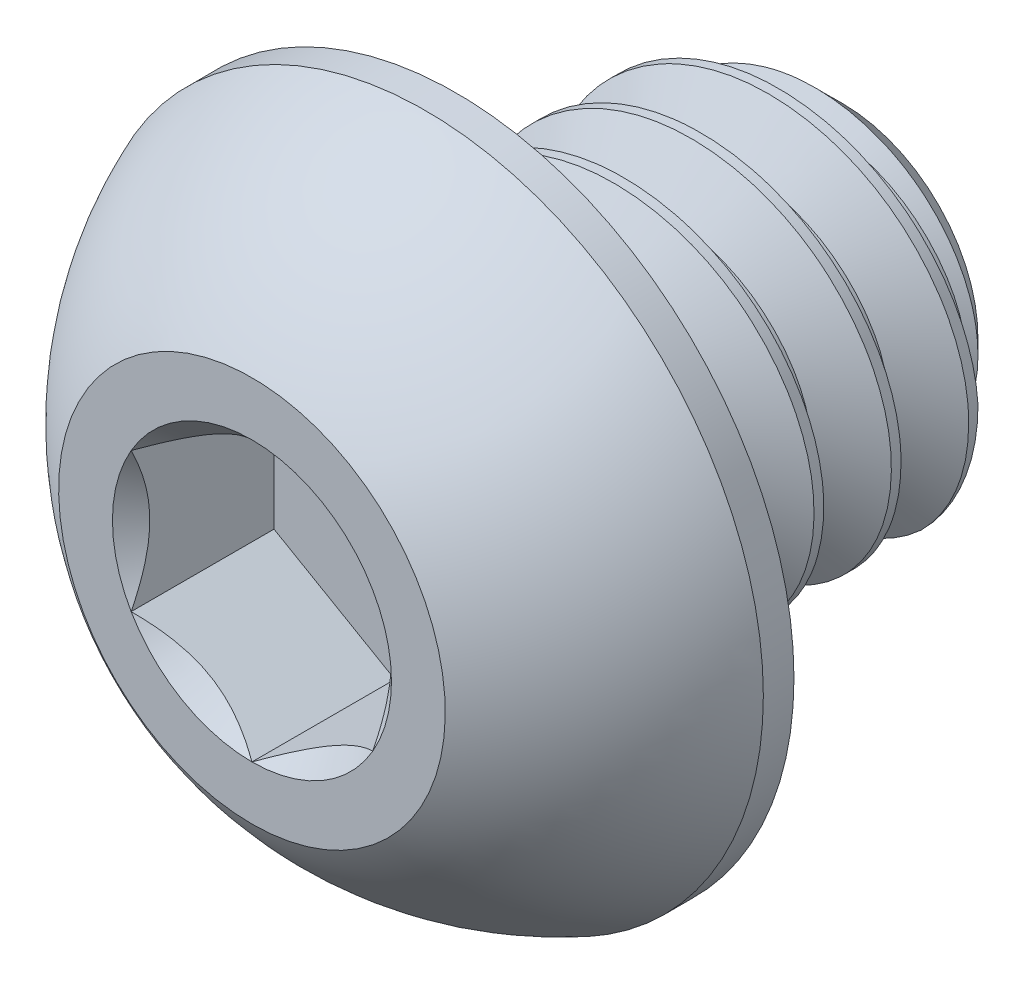
SolidWorks part; units mm, degrees
ref_plane "Front" through (0, 0, 0) normal (0, 0, 1) x (1, 0, 0)
ref_plane "Top" through (0, 0, 0) normal (0, 1, 0) x (1, 0, 0)
ref_plane "Right" through (0, 0, 0) normal (1, 0, 0) x (0, 0, -1)
sketch "Sketch1" plane through (0, 0, 0) normal (1, 0, 0) x (0, 0, -1)
  line L2 (3.3528, 3.175) -> (9.7028, 3.175)
  line L3 (9.7028, 3.175) -> (9.7028, 0)
  line L4 (9.7028, 0) -> (3.3528, 0)
  line L6 (2.8499, 5.5499) -> (3.3528, 5.5499) construction
  line L7 (9.7028, 3.175) -> (9.7028, -3.175) construction
  line L8 (0, 0) -> (3.3528, 0) construction
  line L9 (3.3528, 5.5499) -> (3.3528, -5.5499) construction
  line L11 (3.3528, 3.175) -> (3.3528, 0)
  line L13 (0, 1.9844) -> (0, -1.9844) construction
  line L14 (0, 1.9844) -> (0, 3.175) construction
  arc A3 (0, 3.175) -> (2.8499, 5.5499) centre (5.0603, 0) cw construction
  dimension "D1" = 0.5029
revolve "Revolve1" add sketch "Sketch1" angle 360 mid plane about L4
sketch "Sketch3" plane through (0, 0, -9.7028) normal (0, 0, -1) x (-1, 0, 0)
  circle A0 centre (0, 0) radius 3.175
curve "Helix/Spiral1" pitch 1.27 height 7.62 radius 3.175 centre (0, 0, -9.7028) axis (0, 0, 1) start towards (0, 1, 0)
sketch "Sketch2" plane through (0, 0, 0) normal (1, 0, 0) x (0, 0, -1)
  line L0 (9.7028, 3.175) -> (10.814, 3.175)
  line L1 (10.814, 3.175) -> (10.3378, 2.3501)
  line L2 (10.3378, 2.3501) -> (10.179, 2.3501)
  line L3 (10.179, 2.3501) -> (9.7028, 3.175)
  line L4 (9.9409, 2.7626) -> (10.5759, 2.7626) construction
  dimension "D1" = 60
  dimension "D2" = 0.1588
  dimension "D3" = 0.635
chamfer "Chamfer1" distance 0.9525 angle 45 1 edges at (0, 3.175, -9.7028)
sweep "Cut-Sweep1" cut profiles "Sketch2" path "Helix/Spiral1" align with end faces yes
sketch "Sketch7" plane through (0, 0, 0) normal (1, 0, 0) x (0, 0, -1)
  line L6 (2.8499, 5.5499) -> (3.3528, 5.5499) construction
  line L8 (0, 0) -> (3.3528, 0) construction
  line L11 (3.3528, 5.5499) -> (3.3528, -5.5499) construction
  line L12 (2.8499, 5.5499) -> (3.3528, 5.5499)
  line L13 (0, 0) -> (3.3528, 0)
  line L14 (0, 1.9844) -> (0, -1.9844) construction
  line L15 (3.3528, 5.5499) -> (3.3528, 0)
  line L16 (0, 3.175) -> (0, 0)
  arc A2 (2.8499, 5.5499) -> (0, 3.175) centre (5.0603, 0) ccw construction
  arc A3 (2.8499, 5.5499) -> (0, 3.175) centre (5.0603, 0) ccw
revolve "Revolve2" add sketch "Sketch7" angle 360 mid plane about L13
sketch "Sketch5" plane through (0, 0, 0) normal (0, 0, 1) x (1, 0, 0)
  line L1 (1.9844, -1.1457) -> (1.9844, 1.1457)
  line L2 (1.9844, 1.1457) -> (0, 2.2914)
  line L3 (0, 2.2914) -> (-1.9844, 1.1457)
  line L4 (-1.9844, 1.1457) -> (-1.9844, -1.1457)
  line L5 (-1.9844, -1.1457) -> (0, -2.2914)
  line L6 (0, -2.2914) -> (1.9844, -1.1457)
  circle A0 centre (0, 0) radius 1.9844 construction
extrude "Cut-Extrude2" cut sketch "Sketch5" against normal blind 2.347
sketch "Sketch6" plane through (0, 0, 0) normal (0, 0, 1) x (1, 0, 0)
  circle A0 centre (0, 0) radius 2.2914
extrude "Cut-Extrude3" cut sketch "Sketch6" against normal blind 2.347 draft 45
sketch "Sketch9" [suppressed] plane through (0, 0, -3.3528) normal (0, 0, 1) x (1, 0, 0)
  circle A2 centre (0, 0) radius 3.175
extrude "Boss-Extrude2" [suppressed] add sketch "Sketch9" against normal offset from surface (25.4 mm away) 22.225 up to face at (0, 2.2225, -9.7028)
sketch "Sketch10" plane through (0, 0, 0) normal (1, 0, 0) x (0, 0, -1)
  line L0 (9.7028, 3.175) -> (9.7028, -3.175) construction
  point P0 (7.7978, -3.175)
  dimension "D1" = 1.905
equation "\"D3@Helix/Spiral1\" = \"Lg@Sketch1\" + \"D4@Helix/Spiral1\""
equation "\"D2@Sketch2\" = \"D4@Helix/Spiral1\" * .125"
equation "\"D3@Sketch2\" = \"D4@Helix/Spiral1\" * .5"
equation "\"D1@Chamfer1\" = \"D4@Helix/Spiral1\" * .75"
equation "\"D1@Cut-Extrude2\" = \"Head Ht@Sketch1\" * .7"
equation "\"D1@Sketch1\" = \"Head Ht@Sketch1\" * .15"
equation "\"D1@Sketch10\" = \"D4@Helix/Spiral1\" * 1.5"
equation "\"D1@Cut-Extrude3\" = \"D1@Cut-Extrude2\""
